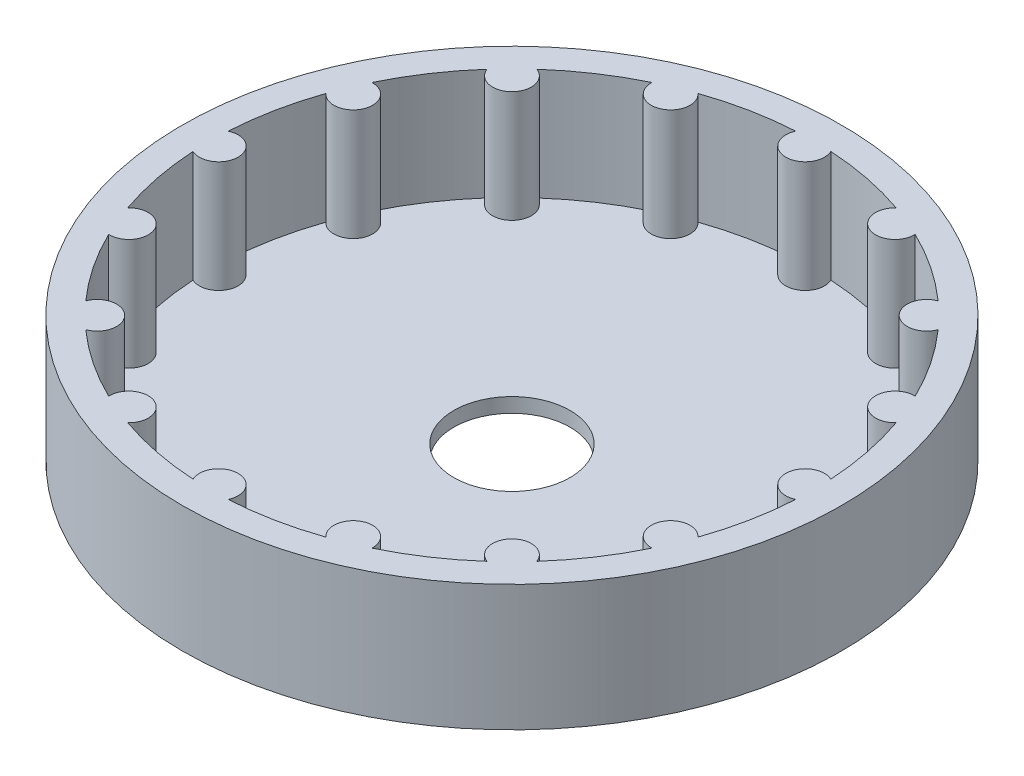
SolidWorks part; units mm, degrees
ref_plane "Front Plane" through (0, 0, 0) normal (0, 0, 1) x (1, 0, 0)
ref_plane "Top Plane" through (0, 0, 0) normal (0, 1, 0) x (1, 0, 0)
ref_plane "Right Plane" through (0, 0, 0) normal (1, 0, 0) x (0, 0, -1)
sketch "Sketch1" plane through (0, 0, 0) normal (0, 1, 0) x (1, 0, 0)
  line L0 (0, 0) -> (0, 60.5) construction
  circle A0 centre (0, 0) radius 60.5 construction
  circle A33 centre (0, 60.5) radius 4
  circle A34 centre (23.1523, 55.8947) radius 4
  circle A35 centre (42.78, 42.78) radius 4
  circle A55 centre (0, 0) radius 68
  circle A56 centre (55.8947, 23.1523) radius 4
  circle A57 centre (60.5, 0) radius 4
  circle A58 centre (55.8947, -23.1523) radius 4
  circle A59 centre (42.78, -42.78) radius 4
  circle A60 centre (23.1523, -55.8947) radius 4
  circle A61 centre (0, -60.5) radius 4
  circle A62 centre (-23.1523, -55.8947) radius 4
  circle A63 centre (-42.78, -42.78) radius 4
  circle A64 centre (-55.8947, -23.1523) radius 4
  circle A65 centre (-60.5, 0) radius 4
  circle A66 centre (-55.8947, 23.1523) radius 4
  circle A67 centre (-42.78, 42.78) radius 4
  circle A68 centre (-23.1523, 55.8947) radius 4
  circle A69 centre (0, 0) radius 62.2827
  circle A70 centre (0, 0) radius 12
  point P34 (1.25, 1.25)
  point P39 (0, 0)
  point P78 (0, 0)
  point P117 (1.25, 1.25)
  dimension "D1" = 121
  dimension "D2" = 8
  dimension "D3" = 136
  dimension "D5" = 24
  dimension "D4" = 16
extrude "Boss-Extrude3" add sketch "Sketch1" along normal blind 23 contours A33 | A55 A69 A61 A62 A63 A64 A65 A66 A67 A68 A33 A34 A35 A56 A57 A58 A59 A60 | A68 | A67 | A66 | A65 | A64 | A63 | A62 | A61 | A60 | A59 | A58 | A57 | A56 | A35 | A34 | A33 region at (0, 0, -59.6968) region at (-66.0767, 0, 0)
extrude "Boss-Extrude4" add sketch "Sketch1<6>" against normal blind 3 contours A55 | A70
sketch "Sketch1<6>" plane through (0, 0, 0) normal (0, 1, 0) x (1, 0, 0) same geometry as "Sketch1"
